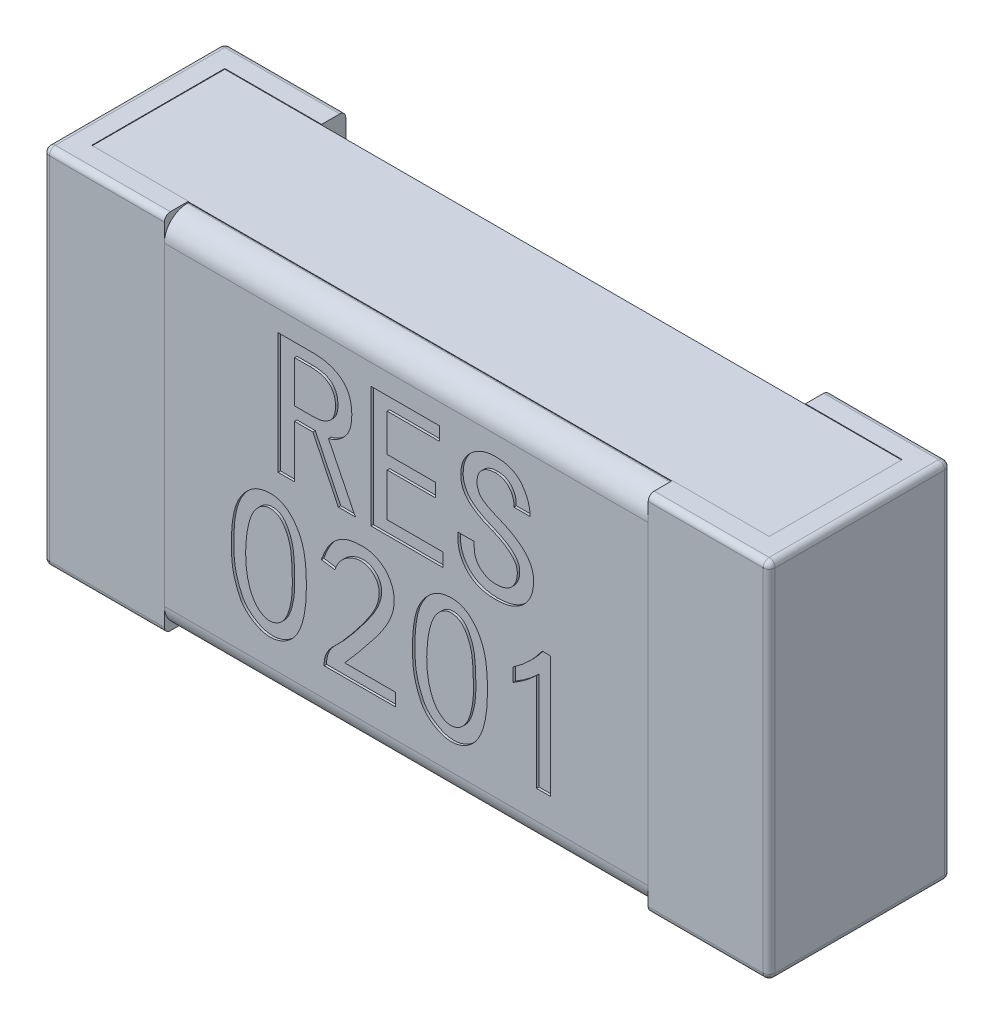
SolidWorks part; units mm, degrees
ref_plane "Front Plane" through (0, 0, 0) normal (0, 0, 1) x (1, 0, 0)
ref_plane "Top Plane" through (0, 0, 0) normal (0, 1, 0) x (1, 0, 0)
ref_plane "Right Plane" through (0, 0, 0) normal (1, 0, 0) x (0, 0, -1)
sketch "Sketch1" plane through (0, 0, 0) normal (0, 0, 1) x (1, 0, 0)
  line L1 (0.28, -0.1495) -> (-0.28, -0.1495)
  line L2 (0.28, -0.1495) -> (0.28, 0.1495)
  line L3 (0.28, 0.1495) -> (-0.28, 0.1495)
  line L4 (-0.28, -0.1495) -> (-0.28, 0.1495)
  line L5 (0.28, -0.1495) -> (-0.28, 0.1495) construction
  line L6 (0.28, 0.1495) -> (-0.28, -0.1495) construction
  point P0 (0, 0)
  dimension "D1" = 0.56
  dimension "D2" = 0.299
extrude "Boss-Extrude1" add sketch "Sketch1" along normal blind 0.11 from offset 0.02
sketch "Sketch2" plane through (0, 0, 0) normal (0, 0, 1) x (1, 0, 0)
  line L0 (0, 0.842) -> (0, -1.0117) construction
  line L1 (0, 0) -> (-0.25, 0) construction
  line L2 (0.3, -0.15) -> (0.3, 0.15)
  line L3 (-0.2, -0.15) -> (-0.3, -0.15)
  line L4 (-0.2, -0.15) -> (-0.2, 0.15)
  line L5 (-0.2, 0.15) -> (-0.3, 0.15)
  line L6 (-0.3, -0.15) -> (-0.3, 0.15)
  line L7 (-0.2, -0.15) -> (-0.3, 0.15) construction
  line L8 (-0.2, 0.15) -> (-0.3, -0.15) construction
  line L9 (0.2, -0.15) -> (0.3, -0.15)
  line L10 (0.2, -0.15) -> (0.2, 0.15)
  line L11 (0.2, 0.15) -> (0.3, 0.15)
  dimension "D1" = 0.25
  dimension "D2" = 0.1
  dimension "D3" = 0.3
extrude "Boss-Extrude2" add sketch "Sketch2" along normal blind 0.02 separate body
extrude "Boss-Extrude3" add sketch "Sketch2<2>" along normal blind 0.02 from offset 0.13
sketch "Sketch2<2>" plane through (0, 0, 0) normal (0, 0, 1) x (1, 0, 0) same geometry as "Sketch2"
sketch "Sketch3" plane through (0, 0, 0) normal (0, 0, 1) x (1, 0, 0)
  line L0 (0, 0.5657) -> (0, -0.5029) construction
  line L1 (0, 0) -> (-0.29, 0) construction
  line L2 (0.3, -0.15) -> (0.3, 0.15)
  line L3 (-0.3, -0.15) -> (-0.28, -0.15)
  line L4 (-0.3, -0.15) -> (-0.3, 0.15)
  line L5 (-0.3, 0.15) -> (-0.28, 0.15)
  line L6 (-0.28, -0.15) -> (-0.28, 0.15)
  line L7 (-0.3, -0.15) -> (-0.28, 0.15) construction
  line L8 (-0.3, 0.15) -> (-0.28, -0.15) construction
  line L9 (0.3, -0.15) -> (0.28, -0.15)
  line L10 (0.3, 0.15) -> (0.28, 0.15)
  line L11 (0.28, -0.15) -> (0.28, 0.15)
  dimension "D1" = 0.29
  dimension "D2" = 0.3
  dimension "D3" = 0.02
extrude "Boss-Extrude4" add sketch "Sketch3" along normal blind 0.11 from offset 0.02
sketch "Sketch4" plane through (0, 0, 0) normal (0, 0, 1) x (1, 0, 0)
  line L1 (0.2, -0.149) -> (-0.2, -0.149)
  line L2 (0.2, -0.149) -> (0.2, 0.149)
  line L3 (0.2, 0.149) -> (-0.2, 0.149)
  line L4 (-0.2, -0.149) -> (-0.2, 0.149)
  line L5 (0.2, -0.149) -> (-0.2, 0.149) construction
  line L6 (0.2, 0.149) -> (-0.2, -0.149) construction
  point P0 (0, 0)
  dimension "D1" = 0.4
  dimension "D2" = 0.298
extrude "Boss-Extrude5" add sketch "Sketch4" along normal blind 0.02 from offset 0.13
fillet "Fillet1" radius 0.019 1 edges at (0, 0.149, 0.15) type face fillet first side face at (0, 0, 0.15) second side face at (0, 0.149, 0.14)
fillet "Fillet2" radius 0.019 1 edges at (0, -0.149, 0.15) type face fillet first side face at (0, -0.0095, 0.15) second side face at (0, -0.149, 0.14)
fillet "Fillet3" radius 0.005 1 edges at (-0.3, 0, 0.15) type face fillet first side face at (-0.3, 0, 0.075) second side face at (-0.25, 0, 0.15)
fillet "Fillet6" radius 0.005 1 edges at (-0.3, 0, 0) type face fillet first side face at (-0.3, 0, 0.0725) second side face at (-0.25, 0, 0)
fillet "Fillet4" radius 0.005 3 edges at (-0.3, -0.15, 0.075) (-0.2475, -0.15, 0) (-0.2475, -0.15, 0.15) type face fillet first side face at (-0.2552, -0.15, 0.075) second side face at (-0.2475, 0, 0) second side face at (-0.3, 0, 0.075) second side face at (-0.2475, 0, 0.15)
fillet "Fillet5" radius 0.005 3 edges at (-0.3, 0.15, 0.075) (-0.2475, 0.15, 0) (-0.2475, 0.15, 0.15) type face fillet first side face at (-0.2552, 0.15, 0.075) second side face at (-0.2475, 0.0025, 0) second side face at (-0.3, 0.0025, 0.075) second side face at (-0.2475, 0.0025, 0.15)
fillet "Fillet7" radius 0.005 1 edges at (0.3, 0, 0) type face fillet first side face at (0.3, 0, 0.075) second side face at (0.25, 0, 0)
fillet "Fillet9" radius 0.005 1 edges at (0.3, 0, 0.15) type face fillet first side face at (0.25, 0, 0.15) second side face at (0.3, 0, 0.0775)
fillet "Fillet8" radius 0.005 3 edges at (0.3, -0.15, 0.075) (0.2475, -0.15, 0.15) (0.2475, -0.15, 0) type face fillet first side face at (0.2552, -0.15, 0.075) second side face at (0.2475, 0, 0.15) second side face at (0.3, 0, 0.075) second side face at (0.2475, 0, 0)
fillet "Fillet10" radius 0.005 3 edges at (0.3, 0.15, 0.075) (0.2475, 0.15, 0.15) (0.2475, 0.15, 0) type face fillet first side face at (0.2552, 0.15, 0.075) second side face at (0.2475, 0.0025, 0) second side face at (0.2475, 0.0025, 0.15) second side face at (0.3, 0.0025, 0.075)
sketch "Sketch6" plane through (0, 0, 0.15) normal (0, 0, 1) x (1, 0, 0)
  line L0 (-0.3, 0.01) -> (0.3, 0.01) construction
  line L1 (-0.3, -0.11) -> (0.3, -0.11) construction
  text T0 "RES" font "黑体" height 0.1
  text T1 "0201" font "黑体" height 0.1
extrude "Cut-Extrude1" cut sketch "Sketch6" against normal blind 0.002
